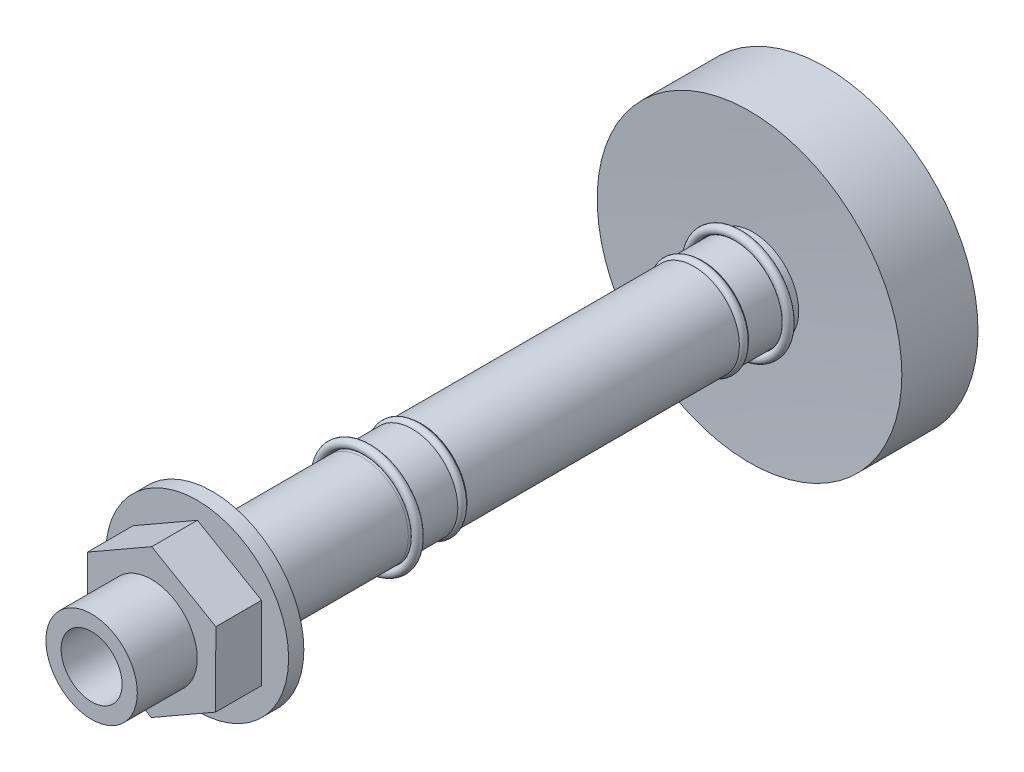
SolidWorks part; units mm, degrees
ref_plane "Front Plane" through (0, 0, 0) normal (0, 0, 1) x (1, 0, 0)
ref_plane "Top Plane" through (0, 0, 0) normal (0, 1, 0) x (1, 0, 0)
ref_plane "Right Plane" through (0, 0, 0) normal (1, 0, 0) x (0, 0, -1)
sketch "Sketch2" plane through (0, 0, 0) normal (1, 0, 0) x (0, 0, -1)
  line L0 (-82.8882, 0) -> (83.7577, 0) construction
  line L1 (-68.6871, 10) -> (-54.1961, 10)
  line L2 (-54.1961, 10) -> (-54.1961, 5.2)
  line L3 (-54.1961, 5.2) -> (54.6949, 5.2)
  line L4 (54.6949, 5.2) -> (54.6949, 10)
  line L5 (54.6949, 10) -> (94.6949, 10)
  line L6 (94.6949, 10) -> (94.6949, 50)
  line L7 (94.6949, 50) -> (69.6949, 50)
  line L9 (94.6949, 15) -> (-106.2603, 15)
  line L11 (-106.5979, 30) -> (-126.5979, 30)
  line L12 (-126.5979, 30) -> (-126.5979, 15)
  line L13 (-126.5979, 15) -> (-146.2603, 15)
  line L14 (-146.2603, 15) -> (-146.2603, 10)
  line L15 (-146.2603, 10) -> (-68.6871, 10)
  line L16 (94.6949, 15) -> (70.8397, 15)
  arc A0 (-106.2603, 15) -> (-106.5979, 30) centre (-1106.1478, 0) ccw
  arc A1 (70.8397, 15) -> (69.6949, 50) centre (-1137.5099, -7.0071) ccw
  dimension "D14" = 2000
  dimension "D12" = 2417.1
  dimension "D2" = 5.2
  dimension "D3" = 10
  dimension "D4" = 10
  dimension "D5" = 5
  dimension "D6" = 30
  dimension "D7" = 50
  dimension "D8" = 40
  dimension "D9" = 15
  dimension "D10" = 20
  dimension "D11" = 25
  dimension "D13" = 177.1
  dimension "D15" = 40
revolve "Revolve1" add sketch "Sketch2" angle 360 about L0 region at (0, 12.7269, 32.612) region at (0, 32.6372, -82.5211)
sketch "Sketch3" plane through (0, 0, 0) normal (0, 1, 0) x (1, 0, 0)
  line L1 (9.7804, 61.4892) -> (4.7804, 61.4892)
  line L2 (9.7804, 61.4892) -> (9.7804, 49.4892)
  line L3 (9.7804, 49.4892) -> (4.7804, 49.4892)
  line L4 (4.7804, 61.4892) -> (4.7804, 49.4892)
  line L5 (0, 27.0222) -> (0, -36.1697) construction
  line L6 (9.9377, -54.2645) -> (4.9377, -54.2645)
  line L7 (9.9377, -54.2645) -> (9.9377, -66.2645)
  line L8 (9.9377, -66.2645) -> (4.9377, -66.2645)
  line L9 (4.9377, -54.2645) -> (4.9377, -66.2645)
  dimension "D1" = 5
  dimension "D2" = 12
  dimension "D3" = 5
  dimension "D4" = 12
revolve "Revolve2" add sketch "Sketch3" angle 360 about L5
sketch "Sketch4" plane through (0, 0, 0) normal (0, 1, 0) x (1, 0, 0)
  line L1 (5.1844, 46.1353) -> (7.1844, 46.1342)
  line L2 (5.1844, 46.1353) -> (5.1844, 43.1342)
  line L3 (5.1844, 43.1342) -> (7.1844, 43.1342)
  line L4 (7.1844, 46.1342) -> (7.1844, 43.1342)
  line L5 (5.1671, -46.0486) -> (7.1671, -46.0486)
  line L6 (5.1671, -46.0486) -> (5.1671, -49.0486)
  line L7 (5.1671, -49.0486) -> (7.1671, -49.0486)
  line L8 (7.1671, -46.0486) -> (7.1671, -49.0486)
  line L14 (15.0008, 54.3777) -> (13.0008, 54.3777)
  line L15 (15.0008, 54.3777) -> (15.0008, 51.3777)
  line L16 (15.0008, 51.3777) -> (13.0008, 51.3777)
  line L17 (13.0008, 54.3777) -> (13.0008, 51.3777)
  line L23 (0, 31.3382) -> (0, -16.0514) construction
  line L24 (15.0082, -38.0516) -> (13.0082, -38.0516)
  line L25 (15.0082, -38.0516) -> (15.0082, -41.0516)
  line L26 (15.0082, -41.0516) -> (13.0082, -41.0516)
  line L27 (13.0082, -38.0516) -> (13.0082, -41.0516)
  line L28 (14.9998, -55.3051) -> (17.9998, -55.3051)
  line L34 (14.9998, -55.3051) -> (14.9998, -57.3051)
  line L35 (14.9998, -57.3051) -> (17.9998, -57.3051)
  line L36 (17.9998, -55.3051) -> (17.9998, -57.3051)
  line L38 (15.0065, 65.3648) -> (18.0065, 65.3648)
  line L39 (15.0065, 65.3648) -> (15.0065, 67.3648)
  line L40 (15.0065, 67.3648) -> (18.0065, 67.3648)
  line L41 (18.0065, 65.3648) -> (18.0065, 67.3648)
  dimension "D1" = 3
  dimension "D2" = 2
  dimension "D3" = 2
  dimension "D4" = 3
  dimension "D5" = 2
  dimension "D6" = 3
  dimension "D7" = 2
  dimension "D8" = 3
  dimension "D9" = 2
  dimension "D10" = 3
  dimension "D11" = 2
  dimension "D12" = 3
revolve "Cut-Revolve1" cut sketch "Sketch4" angle 360 about L23
sketch "Sketch5" plane through (0, 0, 0) normal (0, 1, 0) x (1, 0, 0)
  line L0 (0, 40.6102) -> (0, 26.4444) construction
  circle A0 centre (16.501, 65.8942) radius 1.4
  circle A1 centre (14.4375, 52.8864) radius 1.4
  circle A2 centre (5.7322, 44.6572) radius 1.4
  circle A3 centre (14.4375, -39.5674) radius 1.4
  circle A4 centre (5.7322, -47.5621) radius 1.4
  circle A5 centre (16.501, -55.8575) radius 1.4
  dimension "D1" = 2.8
  dimension "D2" = 2.8
  dimension "D3" = 2.8
  dimension "D4" = 2.8
  dimension "D5" = 2.8
  dimension "D6" = 2.8
revolve "Revolve3" add sketch "Sketch5" angle 360 about L0
sketch "Sketch6" plane through (0, 0, 126.5979) normal (0, 0, 1) x (1, 0, 0)
  line L0 (0, 0) -> (21.0689, -0.0664) construction
  line L1 (21.0306, -12.2305) -> (21.1072, 12.0977)
  line L2 (21.1072, 12.0977) -> (0.0767, 24.3283)
  line L3 (0.0767, 24.3283) -> (-21.0306, 12.2305)
  line L4 (-21.0306, 12.2305) -> (-21.1072, -12.0977)
  line L5 (-21.1072, -12.0977) -> (-0.0767, -24.3283)
  line L6 (-0.0767, -24.3283) -> (21.0306, -12.2305)
  line L7 (0, 0) -> (21.1072, 12.0977) construction
  circle A0 centre (0, 0) radius 21.069 construction
  circle A1 centre (0, 0) radius 30
extrude "Cut-Extrude1" cut sketch "Sketch6" against normal blind 15
equation "\"mountAngle\"=70.9702deg"
equation "\"ThrusterDim\"=160.5mm"
equation "\"hatchHoleDiameter\"=600mm"
equation "\"hullThickness\"=177.1mm"
equation "\"gasketHullInterconnectWidth\"=100mm"
equation "\"collarThickness\"=20mm"
equation "\"hatchTunnelLength\"=200mm"
equation "\"oRingDiameter\"=2mm"
equation "\"boltPatternRadiusInterconnect\"=500mm"
equation "\"interconnectBoltDiameter\"=30mm"
equation "\"hatchShaftDiameter\"=20mm"
equation "\"hatchMinima\"=39.9mm"
equation "\"hullDiameter\"=2240mm"
equation "\"hatchMaxima\"=180mm"
equation "\"bushingFlatHatch\"=15mm"
equation "\"hingePivotDiameter\"=20mm"
equation "\"handleWidth\"=250mm"
equation "\"handleHeight\"=160mm"
equation "\"handleThickness\"=25mm"
equation "\"FrameLength\"=2600mm"
equation "\"FrameMidLength\"=1800mm"
equation "\"TubeOD\"=100mm"
equation "\"FrameBackFlat\"=500mm"
equation "\"TubeWall\"=15.0001mm"
equation "\"TopMemberAngle\"=140deg"
equation "\"FrameHight\"=2500mm"
equation "\"D12@Sketch2\"=\"hullThickness\" + \"hullDiameter\""
equation "\"D13@Sketch2\"=\"hullThickness\""
